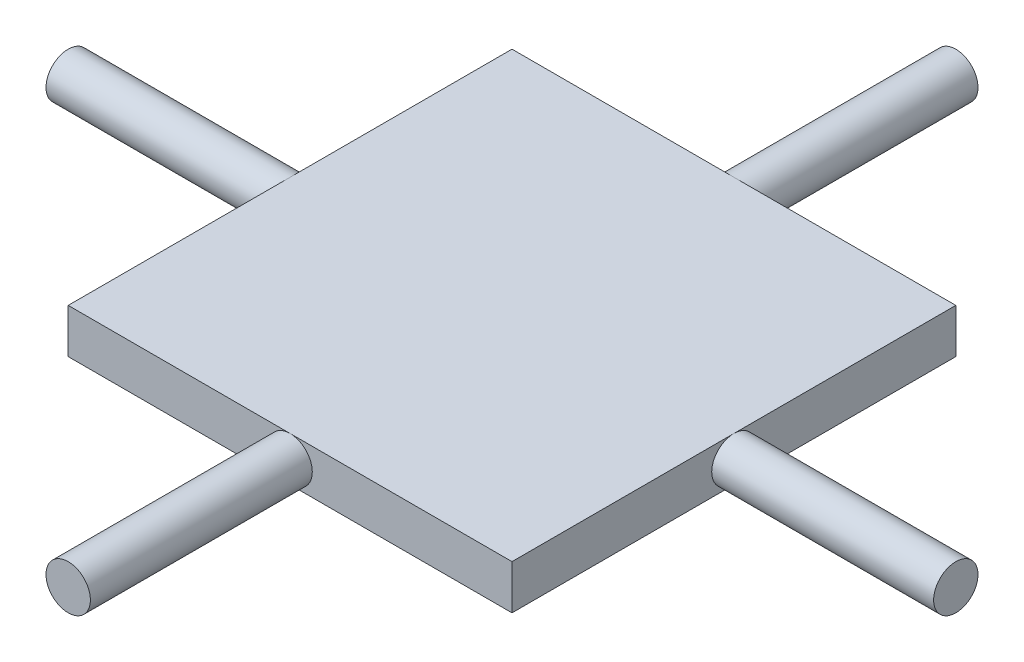
SolidWorks part; units mm, degrees
ref_plane "Front Plane" through (0, 0, 0) normal (0, 0, 1) x (1, 0, 0)
ref_plane "Top Plane" through (0, 0, 0) normal (0, 1, 0) x (1, 0, 0)
ref_plane "Right Plane" through (0, 0, 0) normal (1, 0, 0) x (0, 0, -1)
sketch "Sketch2" plane through (0, 0, 0) normal (0, 1, 0) x (1, 0, 0)
  line L1 (-50, -50) -> (50, -50)
  line L2 (-50, -50) -> (-50, 50)
  line L3 (-50, 50) -> (50, 50)
  line L4 (50, -50) -> (50, 50)
  line L5 (-50, -50) -> (50, 50) construction
  line L6 (-50, 50) -> (50, -50) construction
  point P0 (0, 0)
extrude "Boss-Extrude1" add sketch "Sketch2" along normal blind 5
sketch "Sketch3" plane through (0, 0, 0) normal (0, -1, 0) x (1, 0, 0)
  line L1 (-50, -50) -> (50, -50)
  line L2 (-50, -50) -> (-50, 50)
  line L3 (-50, 50) -> (50, 50)
  line L4 (50, -50) -> (50, 50)
  line L5 (-50, -50) -> (50, 50) construction
  line L6 (-50, 50) -> (50, -50) construction
  point P0 (0, 0)
extrude "Boss-Extrude2" add sketch "Sketch3" along normal blind 5
sketch "Sketch4" plane through (0, 0, 50) normal (0, 0, 1) x (1, 0, 0)
  circle A0 centre (0, 0) radius 5
extrude "Boss-Extrude3" add sketch "Sketch4" along normal blind 50
sketch "Sketch5" plane through (-50, 0, 0) normal (-1, 0, 0) x (0, 0, 1)
  circle A0 centre (0, 0) radius 5
extrude "Boss-Extrude4" add sketch "Sketch5" along normal blind 50
sketch "Sketch6" plane through (0, 0, -50) normal (0, 0, -1) x (-1, 0, 0)
  circle A0 centre (0, 0) radius 5
extrude "Boss-Extrude5" add sketch "Sketch6" along normal blind 50
sketch "Sketch7" plane through (50, 0, 0) normal (1, 0, 0) x (0, 0, -1)
  circle A0 centre (0, 0) radius 5
extrude "Boss-Extrude6" add sketch "Sketch7" along normal blind 50
